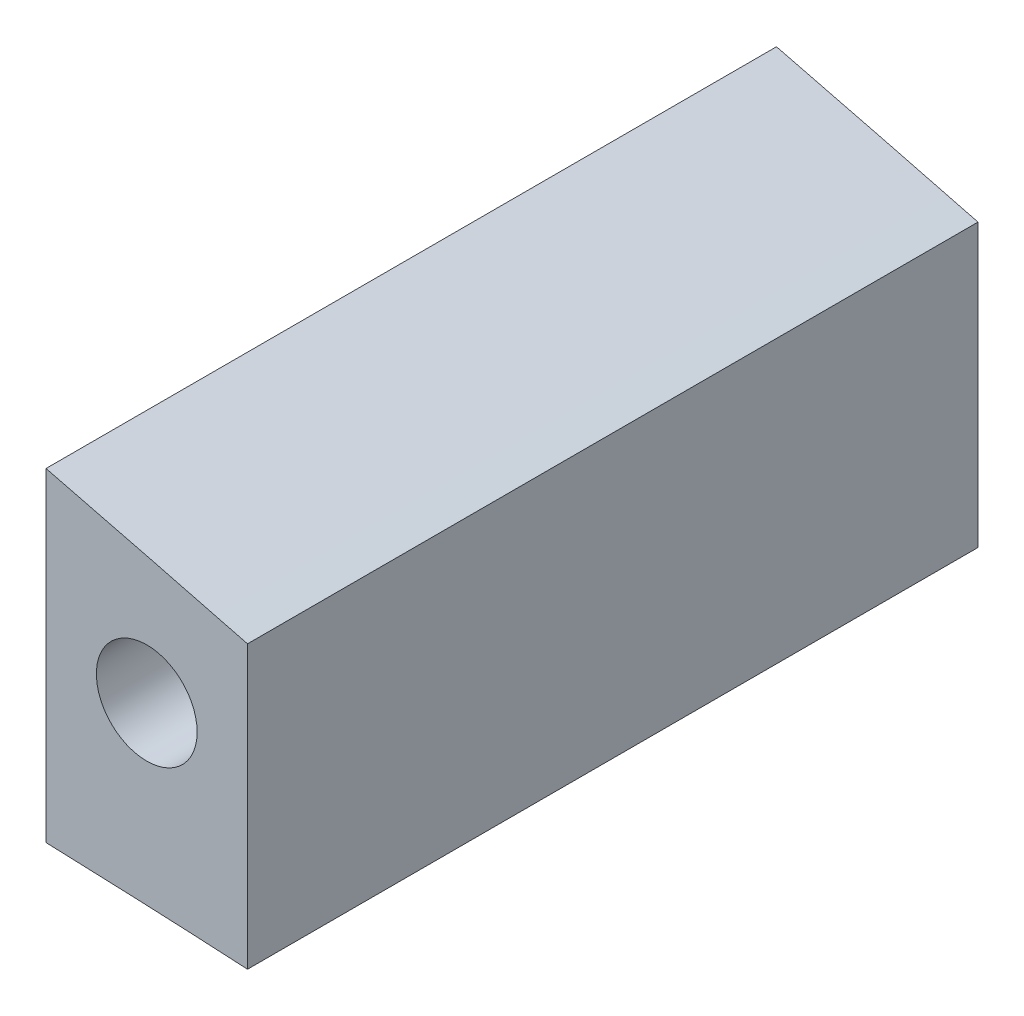
SolidWorks part; units mm, degrees
ref_plane "Front Plane" through (0, 0, 0) normal (0, 0, 1) x (1, 0, 0)
ref_plane "Top Plane" through (0, 0, 0) normal (0, 1, 0) x (1, 0, 0)
ref_plane "Right Plane" through (0, 0, 0) normal (1, 0, 0) x (0, 0, -1)
sketch "Sketch1" plane through (0, 0, 0) normal (0, 0, 1) x (1, 0, 0)
  spline S0 degree 3 poles (0.0006, 0.0001) (0.8106, 7.3592) (8.6491, 17.8566) (26.2867, 29.9752) (52.1111, 42.0692) (89.5976, 49.2908) (131.4008, 47.8848) (173.2567, 40.0411) (217.9611, 29.613) (256.9521, 19.5289) (290.3598, 8.711) (301.2732, 4.3828) (314.8169, -0.5162) (309.8463, 0.0001) knots 0 0 0 0 0.060864 0.113688 0.188609 0.312909 0.448482 0.557612 0.691544 0.852438 0.929756 0.976058 1 1 1 1
  spline S1 degree 3 poles (309.8463, 0.0001) (303.9568, 1.471) (293.9895, 2.094) (276.264, 4.5144) (260.8463, 5.4274) (235.8588, 7.8703) (205.1014, 8.8381) (157.7186, 9.0307) (110.4973, 6.1815) (66.5062, -0.5867) (36.4547, -6.0985) (15.3166, -6.1891) (1.2307, -6.9241) (0.0006, 0.0001) knots 0 0 0 0 0.057787 0.095275 0.171021 0.205339 0.335319 0.464904 0.658702 0.785512 0.893517 0.943092 1 1 1 1
extrude "Boss-Extrude1" add sketch "Sketch1" along normal blind 46.0375
sketch "Sketch2" plane through (0, 0, 46.0375) normal (0, 0, 1) x (1, 0, 0)
  circle A0 centre (20.32, 10.16) radius 6.35
  circle A1 centre (227.2963, 19.0501) radius 3.175
  dimension "D2" = 12.7
  dimension "D3" = 6.35
  dimension "D6" = 20.32
  dimension "D1" = 82.55
  dimension "D4" = 19.05
  dimension "D5" = 10.16
extrude "Cut-Extrude1" cut sketch "Sketch2" against normal through all
sketch "Sketch3" plane through (0, 0, 46.0375) normal (0, 0, 1) x (1, 0, 0)
  line L1 (350.4863, -6.3499) -> (233.6463, -6.3499)
  line L2 (350.4863, -6.3499) -> (350.4863, 44.4501)
  line L3 (350.4863, 44.4501) -> (233.6463, 44.4501)
  line L4 (233.6463, -6.3499) -> (233.6463, 44.4501)
  circle A0 centre (227.2963, 19.0501) radius 3.175 construction
  dimension "D1" = 6.35
  dimension "D2" = 116.84
  dimension "D3" = 50.8
  dimension "D4" = 44.45
extrude "Cut-Extrude2" cut sketch "Sketch3" against normal through all contours L3 L4 L1 L2
sketch "Sketch4" plane through (0, 0, 46.0375) normal (0, 0, 1) x (1, 0, 0)
  line L0 (233.6463, 7.6905) -> (233.6463, 25.4528) construction
  line L1 (220.9463, -24.2166) -> (-29.2042, -24.2166)
  line L2 (220.9463, -24.2166) -> (220.9463, 93.2727)
  line L3 (220.9463, 93.2727) -> (-29.2042, 93.2727)
  line L4 (-29.2042, -24.2166) -> (-29.2042, 93.2727)
  dimension "D1" = 12.7
extrude "Cut-Extrude3" cut sketch "Sketch4" against normal through all
